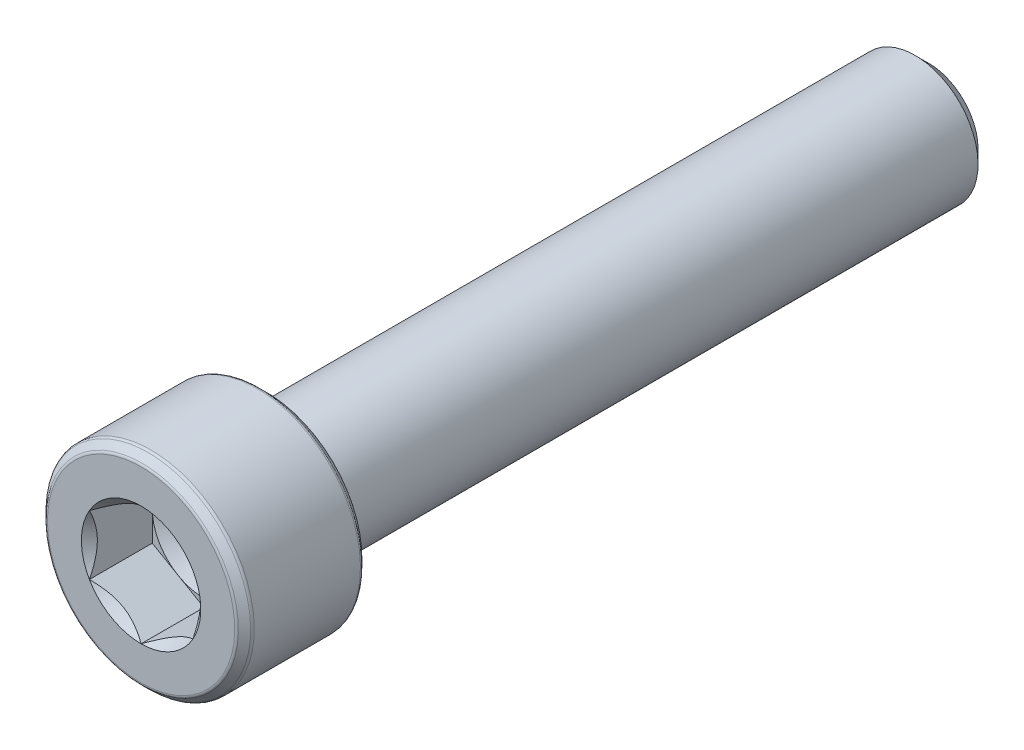
SolidWorks part; units mm, degrees
ref_plane "Front Plane" through (0, 0, 0) normal (0, 0, 1) x (1, 0, 0)
ref_plane "Top Plane" through (0, 0, 0) normal (0, 1, 0) x (1, 0, 0)
ref_plane "Right Plane" through (0, 0, 0) normal (1, 0, 0) x (0, 0, -1)
sketch "Sketch1" plane through (0, 0, 0) normal (1, 0, 0) x (0, 0, -1)
  line L0 (-15.113, 0) -> (15.113, 0) construction
  line L1 (-15.113, 0) -> (-15.113, 3.9688)
  line L2 (-15.113, 3.9688) -> (-10.287, 3.9688)
  line L3 (-10.287, 3.9688) -> (-10.287, 2.413)
  line L4 (-10.287, 2.413) -> (14.5974, 2.413)
  line L5 (15.0634, 2.4989) -> (15.4603, 1.8115) construction
  line L6 (15.4603, 1.8115) -> (15.8571, 2.4989) construction
  line L7 (15.8571, 2.4989) -> (15.0634, 2.4989) construction
  line L8 (14.5974, 2.413) -> (15.113, 1.8974)
  line L9 (15.113, 1.8974) -> (15.113, 0)
  line L10 (15.113, 2.413) -> (15.8075, 2.413) construction
  line L11 (15.4603, 2.4989) -> (15.4603, 2.413) construction
  line L12 (15.4603, 2.413) -> (15.4603, 1.8974) construction
  line L13 (15.4603, 1.8974) -> (15.4603, 1.8115) construction
  line L14 (15.4107, 1.8974) -> (15.5099, 1.8974)
  line L15 (15.0882, 2.456) -> (15.8323, 2.456)
  line L16 (15.5099, 1.8974) -> (15.8323, 2.456)
  line L17 (15.4107, 1.8974) -> (15.0882, 2.456)
  line L18 (-15.113, 1.9844) -> (-12.7, 1.9844)
  line L19 (-12.7, 1.9844) -> (-12.7, 0)
  line L20 (13.1286, 2.413) -> (13.1286, -2.413) construction
  point P20 (15.4603, 2.456)
  point P22 (13.1286, -2.413)
  point P28 (13.1286, 0)
  point P29 (14.5974, -2.413)
  point P30 (-11.4935, 3.9688)
  dimension "Head Diameter" = 7.9375
  dimension "Length" = 25.4
  dimension "Head Height" = 4.826
  dimension "Screw Size Decimal Equivalent" = 4.826
  dimension "D1" = 45
  dimension "Thread Pitch" = 0.7937
  dimension "D3" = 0.0992
  dimension "Drive Size" = 3.9688
  dimension "D4" = 1.9844
  dimension "D5" = 2.413
  dimension "D2" = 3.6195
sketch "Sketch3" plane through (0, 0, 0) normal (1, 0, 0) x (0, 0, -1)
  line L0 (-15.113, 3.5937) -> (-15.113, 1.9844)
  line L1 (-15.113, 1.9844) -> (-12.7, 1.9844)
  line L2 (-12.7, 1.9844) -> (-12.7, 0)
  line L3 (-12.7, 0) -> (15.113, 0)
  line L4 (15.113, 0) -> (15.113, 1.8974)
  line L5 (15.113, 1.8974) -> (14.5974, 2.413)
  line L6 (14.5974, 2.413) -> (-10.287, 2.413)
  line L7 (-10.287, 2.413) -> (-10.287, 3.5937)
  line L8 (-10.662, 3.9688) -> (-14.738, 3.9688)
  line L9 (-15.0723, 3.6919) -> (-14.8362, 3.9281)
  line L10 (-10.5638, 3.9281) -> (-10.3277, 3.6919)
  line L11 (-15.113, 3.9688) -> (-10.287, 3.9688) construction
  arc A0 (-14.8362, 3.9281) -> (-14.738, 3.9688) centre (-14.738, 3.8298) cw
  arc A1 (-15.0723, 3.6919) -> (-15.113, 3.5937) centre (-14.9741, 3.5937) ccw
  arc A2 (-10.3277, 3.6919) -> (-10.287, 3.5937) centre (-10.4259, 3.5937) cw
  arc A3 (-10.5638, 3.9281) -> (-10.662, 3.9688) centre (-10.662, 3.8298) ccw
  point P25 (-15.113, 3.6513)
  dimension "D3" = 0.1389
  dimension "D1" = 45
  dimension "D2" = 0.3175
revolve "Revolve1" add sketch "Sketch3" angle 360 about L0
sketch "Sketch4" plane through (0, 0, 15.113) normal (0, 0, 1) x (1, 0, 0)
  line L1 (0, 2.2914) -> (-1.9844, 1.1457)
  line L2 (-1.9844, 1.1457) -> (-1.9844, -1.1457)
  line L3 (-1.9844, -1.1457) -> (0, -2.2914)
  line L4 (0, -2.2914) -> (1.9844, -1.1457)
  line L5 (1.9844, -1.1457) -> (1.9844, 1.1457)
  line L6 (1.9844, 1.1457) -> (0, 2.2914)
  circle A0 centre (0, 0) radius 1.9844 construction
extrude "Cut-Extrude1" cut sketch "Sketch4" against normal up to vertex (2.413 mm away) up to point (0, 1.9844, 12.7)
sketch "Sketch5" plane through (0, 0, 15.113) normal (0, 0, 1) x (1, 0, 0)
  circle A0 centre (0, 0) radius 2.2914
extrude "Cut-Extrude2" cut sketch "Sketch5" against normal up to next (2.413 mm away) draft 45
sketch "Sketch10" plane through (0, 0, 12.7) normal (0, 0, 1) x (1, 0, 0)
  line L0 (1.9844, 1.1457) -> (1.9844, -1.1457) construction
  circle A0 centre (0, 0) radius 1.9844
extrude "Cut-Extrude3" cut sketch "Sketch10" against normal through all draft 60
ref_plane "Plane1" [suppressed] through (0, 0, 10.1878) normal (0, 0, -1) x (-1, 0, 0)
split "Split1" [suppressed] bodies to split 112
sketch "Sketch6" [suppressed] plane through (0, 0, -15.113) normal (0, 0, -1) x (-1, 0, 0)
  circle A0 centre (0, 0) radius 2.413 construction
  circle A1 centre (0, 0) radius 2.413
curve "Helix/Spiral1" [suppressed] pitch 0.7937 height 26.1937 turns 33
sketch "Sketch7" [suppressed] plane through (0, 0, 0) normal (1, 0, 0) x (0, 0, -1)
  line L0 (15.4107, 1.8974) -> (15.5099, 1.8974) construction
  line L1 (15.4107, 1.8974) -> (15.0882, 2.456) construction
  line L2 (15.0882, 2.456) -> (15.8323, 2.456) construction
  line L3 (15.5099, 1.8974) -> (15.8323, 2.456) construction
  line L4 (15.4107, 1.8974) -> (15.5099, 1.8974)
  line L5 (15.4107, 1.8974) -> (15.0882, 2.456)
  line L6 (15.0882, 2.456) -> (15.8323, 2.456)
  line L7 (15.5099, 1.8974) -> (15.8323, 2.456)
sweep "Cut-Sweep1" [suppressed] cut profiles "Sketch7" path "Helix/Spiral1"
sketch "Sketch14" [suppressed] plane through (0, 0, 10.1878) normal (0, 0, -1) x (-1, 0, 0)
  circle A1 centre (0, 0) radius 2.413
  circle A2 centre (0, 0) radius 2.413
  dimension "D1" = 0
extrude "Boss-Extrude2" [suppressed] add sketch "Sketch14" along normal through all draft 59.977
sketch "Sketch12" [suppressed] plane through (0, 0, 15.113) normal (0, 0, 1) x (1, 0, 0)
  line L0 (0, 0) -> (0, 3.9688) construction
  line L1 (0, 0) -> (0.1984, 4.2381) construction
  line L2 (0.1984, 4.2381) -> (-0.1984, 4.2381)
  line L3 (-0.1984, 4.2381) -> (0, 0) construction
  line L4 (-0.1984, 4.2381) -> (-0.0458, 3.8718)
  line L5 (0.0458, 3.8718) -> (0.1984, 4.2381)
  line L7 (0, 3.5937) -> (0, 3.6919) construction
  circle A0 centre (0, 0) radius 3.9688 construction
  arc A2 (-0.0458, 3.8718) -> (0.0458, 3.8718) centre (0, 3.8909) ccw
  point P11 (0, 3.7619)
  point P13 (0, 3.8413)
  point P17 (0, 3.6428)
  dimension "D3" = 0.0496
  dimension "D1" = 0.3969
  dimension "D2" = 5.361
  dimension "D5" = 0.1984
extrude "Cut-Extrude4" [suppressed] cut sketch "Sketch12" against normal blind 3.6195
sketch "Sketch13" [suppressed] plane through (0, 0, 11.4935) normal (0, 0, 1) x (1, 0, 0)
  circle A0 centre (0, 0) radius 3.9688
  circle A2 centre (0, 0) radius 2.413
  arc A3 (0.0858, 3.9678) -> (-0.0858, 3.9678) centre (0, 0) ccw construction
extrude "Boss-Extrude1" [suppressed] add sketch "Sketch13" along normal through all draft 45
pattern_circular "CirPattern1" [suppressed] count 72 over 360 about axis through (0, 0, 15.113) along (0, 0, -1) of bodies 116
equation "\"D3@Sketch1\" = \"Thread Pitch@Sketch1\" / 8"
equation "\"D4@Sketch1\"=\"Thread Pitch@Sketch1\" * 2.5"
equation "\"D3@Helix/Spiral1\"=\"Length@Sketch1\" + \"Thread Pitch@Sketch1\""
equation "\"D4@Helix/Spiral1\" = \"Thread Pitch@Sketch1\""
equation "\"D5@Sketch1\"=\"Head Height@Sketch1\"*0.5"
equation "\"D2@Sketch3\"=\"Head Diameter@Sketch1\" /25"
equation "\"D1@Sketch12\"=\"Head Diameter@Sketch1\"*0.05"
equation "\"D1@CirPattern1\"=int(360/\"D2@Sketch12\")+5"
equation "\"D3@Sketch12\"=\"D1@Sketch12\"*0.125"
equation "\"D3@Sketch3\"=\"D2@Sketch3\"*0.4375"
equation "\"D5@Sketch12\"=\"D2@Sketch3\"*0.625"
equation "\"D1@Cut-Extrude4\"=\"D2@Sketch1\""
equation "\"D2@Sketch1\"=\"Head Height@Sketch1\"*0.75"
equation "\"D1@Plane1\"=\"Thread Pitch@Sketch1\"*0.125"
equation "\"Pitch Natural Taper Angle\"= ATN ( \"Thread Pitch@Sketch1\" / 2 )"
equation "\"Angle Count\"= 60 / \"Pitch Natural Taper Angle\""
equation "\"Rounded Angle Count\"= ROUND ( \"Angle Count\" )"
equation "\"Taper Angle\"= \"Rounded Angle Count\" * \"Pitch Natural Taper Angle\""
equation "\"D3@Boss-Extrude2\"=\"Taper Angle\""
